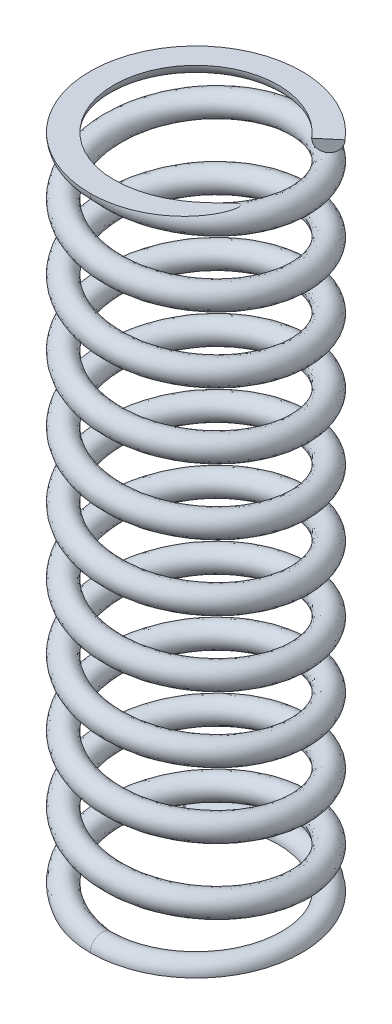
SolidWorks part; units mm, degrees
ref_plane "Przednia" through (0, 0, 0) normal (0, 0, 1) x (1, 0, 0)
ref_plane "Górna" through (0, 0, 0) normal (0, 1, 0) x (1, 0, 0)
ref_plane "Prawa" through (0, 0, 0) normal (1, 0, 0) x (0, 0, -1)
sketch "Szkic1" plane through (0, 0, 0) normal (0, 1, 0) x (1, 0, 0)
  circle A0 centre (0, 0) radius 2
  dimension "D1" = 4
curve "Helisa/Spirala1" pitch 1.75 height 17.5 radius 2 left hand yes centre (0, 0, 0) axis (0, 1, 0) start towards (0, 0, 1)
sketch "Szkic2" plane through (0, 0, 0) normal (1, 0, 0) x (0, 0, -1)
  line L0 (0, 0) -> (-2.5, 0) construction
  circle A0 centre (-2.5, 0) radius 0.315
  dimension "D1" = 0.63
  dimension "D2" = 2.5
sweep "Wyciągnięcie po ścieżce1" add profiles "Szkic2" path "Helisa/Spirala1"
sketch "Szkic4" [suppressed] plane through (0, 0, 0) normal (0, 0, 1) x (1, 0, 0)
  line L0 (0, 0) -> (0, 17.6191) construction
sketch "Szkic6" plane through (0, 0, 0) normal (0, 1, 0) x (1, 0, 0)
  line L1 (-5.6252, -6.9397) -> (5.6252, -6.9397)
  line L2 (-5.6252, -6.9397) -> (-5.6252, 6.9397)
  line L3 (-5.6252, 6.9397) -> (5.6252, 6.9397)
  line L4 (5.6252, -6.9397) -> (5.6252, 6.9397)
  line L5 (-5.6252, -6.9397) -> (5.6252, 6.9397) construction
  line L6 (-5.6252, 6.9397) -> (5.6252, -6.9397) construction
  point P0 (0, 0)
extrude "Wytnij-wyciągnięcie2" cut sketch "Szkic6" against normal blind 10
sketch "Szkic7" plane through (0, 0, 0) normal (1, 0, 0) x (0, 0, -1)
  line L0 (-2.185, 0) -> (-2.815, 0) construction
  line L1 (-2.185, 0) -> (-2.815, 0)
  arc A0 (-2.185, 0) -> (-2.815, 0) centre (-2.5, 0) ccw construction
  arc A1 (-2.185, 0) -> (-2.815, 0) centre (-2.5, 0) ccw
revolve "Obrót1" add sketch "Szkic7" angle 230 about L0
ref_plane "Płaszczyzna1" through (0, 17.5, 0) normal (0, 1, 0) x (1, 0, 0)
sketch "Szkic8" plane through (0, 17.5, 0) normal (0, 1, 0) x (1, 0, 0)
  line L1 (6.3815, 4.5572) -> (-6.3815, 4.5572)
  line L2 (6.3815, 4.5572) -> (6.3815, -4.5572)
  line L3 (6.3815, -4.5572) -> (-6.3815, -4.5572)
  line L4 (-6.3815, 4.5572) -> (-6.3815, -4.5572)
  line L5 (6.3815, 4.5572) -> (-6.3815, -4.5572) construction
  line L6 (6.3815, -4.5572) -> (-6.3815, 4.5572) construction
  point P0 (0, 0)
extrude "Wytnij-wyciągnięcie3" cut sketch "Szkic8" along normal blind 10
sketch "Szkic9" plane through (0, 0, 0) normal (-1, 0, 0) x (0, 0, 1)
  line L0 (2.185, 17.5) -> (2.815, 17.5) construction
  line L1 (2.185, 17.5) -> (2.815, 17.5)
  arc A0 (2.185, 17.5) -> (2.815, 17.5) centre (2.5, 17.5) ccw construction
  arc A1 (2.185, 17.5) -> (2.815, 17.5) centre (2.5, 17.5) ccw
revolve "Obrót2" add sketch "Szkic9" angle 230 about L0 reverse direction yes
